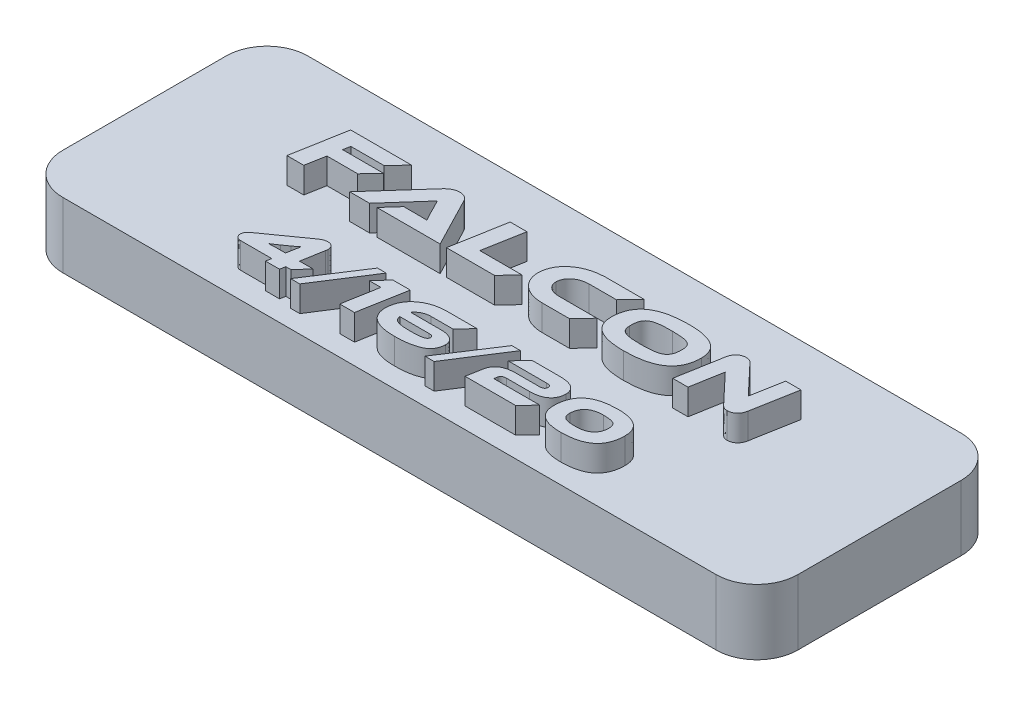
SolidWorks part; units mm, degrees
ref_plane "Front Plane" through (0, 0, 0) normal (0, 0, 1) x (1, 0, 0)
ref_plane "Top Plane" through (0, 0, 0) normal (0, 1, 0) x (1, 0, 0)
ref_plane "Right Plane" through (0, 0, 0) normal (1, 0, 0) x (0, 0, -1)
sketch "Sketch1" plane through (0, 0, 0) normal (0, 1, 0) x (1, 0, 0)
  line L1 (-28.575, 9.525) -> (28.575, 9.525)
  line L2 (-28.575, 9.525) -> (-28.575, -9.525)
  line L3 (-28.575, -9.525) -> (28.575, -9.525)
  line L4 (28.575, 9.525) -> (28.575, -9.525)
  line L5 (-28.575, 9.525) -> (28.575, -9.525) construction
  line L6 (-28.575, -9.525) -> (28.575, 9.525) construction
  point P0 (0, 0)
  dimension "D1" = 57.15
  dimension "D2" = 19.05
extrude "Boss-Extrude1" add sketch "Sketch1" along normal up to surface (5.08 mm away)
fillet "Fillet1" radius 3.175 4 edges at (-28.575, 2.54, 9.525) (-28.575, 2.54, -9.525) (28.575, 2.54, 9.525) (28.575, 2.54, -9.525)
sketch "Sketch3" plane through (0, 5.08, 0) normal (0, 1, 0) x (1, 0, 0)
  line L0 (28.575, -7.9375) -> (-28.575, -7.9375) construction
  line L1 (28.575, -6.35) -> (28.575, 6.35) construction
  line L2 (-28.575, 6.35) -> (-28.575, -6.35) construction
  line L3 (28.575, 0) -> (-28.575, 0) construction
  line L5 (-25.4, -9.525) -> (25.4, -9.525) construction
  line L6 (25.4, 9.525) -> (-25.4, 9.525) construction
  text T0 "Falcon" font "Ethnocentric Rg" height in points 16
  text T1 "4/16/20" font "Ethnocentric Rg" height in points 14
  point P8 (-28.575, 0)
  dimension "D1" = 1.5875
extrude "Boss-Extrude2" add sketch "Sketch3" along normal blind 2
sketch "Sketch4" plane through (0, 0, 0) normal (0, -1, 0) x (1, 0, 0)
  line L0 (25.4, 0) -> (-25.4, 0) construction
  circle A0 centre (-25.4, 0) radius 0.9
  circle A1 centre (25.4, 0) radius 0.9
  point P3 (0, 0)
  dimension "D2" = 1.8
  dimension "D1" = 50.8
extrude "Cut-Extrude1" cut sketch "Sketch4" against normal blind 4
